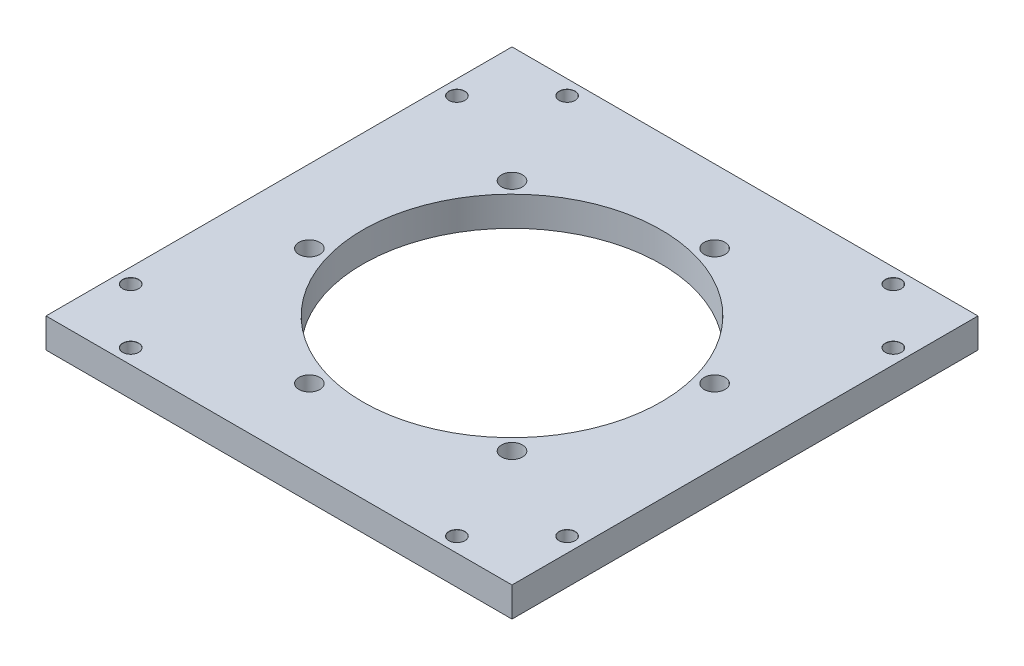
SolidWorks part; units mm, degrees
material "6061 Alloy"
ref_plane "Front Plane" through (0, 0, 0) normal (0, 0, 1) x (1, 0, 0)
ref_plane "Top Plane" through (0, 0, 0) normal (0, 1, 0) x (1, 0, 0)
ref_plane "Right Plane" through (0, 0, 0) normal (1, 0, 0) x (0, 0, -1)
sketch "Sketch1" plane through (0, 0, 0) normal (0, 1, 0) x (1, 0, 0)
  line L1 (-50, -50) -> (50, -50)
  line L2 (-50, -50) -> (-50, 50)
  line L3 (-50, 50) -> (50, 50)
  line L4 (50, -50) -> (50, 50)
  line L5 (-50, -50) -> (50, 50) construction
  line L6 (-50, 50) -> (50, -50) construction
  circle A1 centre (0, 0) radius 39.5
  arc A5 (-25.1023, 25.1023) -> (9.1881, 34.2904) centre (0, 0) cw
  arc A7 (9.1881, 34.2904) -> (-34.2904, -9.1881) centre (0, 0) ccw
  arc A9 (-34.2904, -9.1881) -> (-9.1881, -34.2904) centre (0, 0) ccw
  arc A11 (-9.1881, -34.2904) -> (25.1023, -25.1023) centre (0, 0) ccw
  circle A13 centre (0, 0) radius 32
  arc A14 (25.1023, -25.1023) -> (34.2904, 9.1881) centre (0, 0) ccw
extrude "Boss-Extrude3" add sketch "Sketch1" along normal blind 6.35 contours L1 L4 L3 L2 A1 | A1 A13 region at (-48.5858, 0, 0) region at (-38.3828, 0, 0)
hole_wizard "M4 Clearance Hole2" positions "Sketch6" profile "Sketch7" hole size "M4" standard "ANSI Metric" end condition through all
sketch "Sketch6" plane through (0, 0, 0) normal (0, -1, 0) x (-1, 0, 0)
  point P0 (-9.1881, 34.2904)
  point P3 (25.1023, 25.1023)
  point P6 (34.2904, -9.1881)
  point P9 (9.1881, -34.2904)
  point P12 (-25.1023, -25.1023)
  point P15 (-34.2904, 9.1881)
sketch "Sketch7" plane through (9.1881, 0, -34.2904) normal (1, 0, 0) x (0, 0, -1)
  line L0 (0, 0) -> (0, 6.35)
  line L1 (0, 6.35) -> (2.25, 6.35)
  line L2 (2.25, 6.35) -> (2.25, 0.025)
  line L3 (2.25, 0.025) -> (2.275, 0)
  line L5 (2.275, 0) -> (0, 0)
  line L6 (-2.25, 0.025) -> (-2.275, 0) construction
  line L11 (0, -6.35) -> (0, 107.95) construction
  dimension "Thru Hole Dia." = 4.5
  dimension "Thru Hole Depth" = 6.35
  dimension "Near C'Sink Dia." = 4.55
  dimension "Near C'Sink Angle" = 90
sketch "Sketch8" plane through (0, 6.35, 0) normal (0, 1, 0) x (1, 0, 0)
  line L0 (-50, -50) -> (-39.5, -50)
  line L1 (-50, -50) -> (50, -50) construction
  line L2 (-39.5, -50) -> (-39.5, -39.5)
  line L3 (50, -50) -> (39.5, -50)
  line L4 (39.5, -50) -> (39.5, -39.5)
  line L5 (50, 50) -> (39.5, 50)
  line L6 (-50, 50) -> (50, 50) construction
  line L7 (39.5, 50) -> (39.5, 39.5)
  line L8 (-50, 50) -> (-39.5, 50)
  line L9 (-50, -50) -> (-50, 50) construction
  line L10 (-39.5, 50) -> (-39.5, 39.5)
sketch "Sketch13" plane through (0, 6.35, 0) normal (0, 1, 0) x (1, 0, 0)
  line L1 (-50, -50) -> (-35, -50)
  line L2 (-50, -50) -> (50, -50) construction
  line L3 (-35, -50) -> (-35, -46.825)
  line L4 (-50, -50) -> (-50, -35)
  line L5 (-50, -50) -> (-50, 50) construction
  line L6 (-50, -35) -> (-46.825, -35)
  line L7 (-50, 50) -> (-35, 50)
  line L8 (-50, 50) -> (50, 50) construction
  line L9 (-35, 50) -> (-35, 46.825)
  line L10 (-50, 50) -> (-50, 35)
  line L11 (-50, 35) -> (-46.825, 35)
  line L13 (50, 50) -> (35, 50)
  line L14 (35, 50) -> (35, 46.825)
  line L15 (50, 50) -> (50, 35)
  line L16 (50, -50) -> (50, 50) construction
  line L17 (50, 35) -> (46.825, 35)
  line L18 (50, -50) -> (50, -35)
  line L19 (50, -35) -> (46.825, -35)
  line L20 (50, -50) -> (35, -50)
  line L21 (35, -50) -> (35, -46.825)
hole_wizard "M3 Clearance Hole1" positions "Sketch17" profile "Sketch18" hole size "M3" standard "ANSI Metric" end condition through all
sketch "Sketch17" plane through (0, 6.35, 0) normal (0, 1, 0) x (1, 0, 0)
  point P0 (-46.825, 35)
  point P3 (-35, 46.825)
  point P6 (35, 46.825)
  point P9 (46.825, 35)
  point P12 (46.825, -35)
  point P15 (35, -46.825)
  point P18 (-35, -46.825)
  point P21 (-46.825, -35)
sketch "Sketch18" plane through (-46.825, 6.35, -35) normal (1, 0, 0) x (0, 0, 1)
  line L0 (0, 0) -> (0, 6.35)
  line L1 (0, 6.35) -> (1.7, 6.35)
  line L2 (1.7, 6.35) -> (1.7, 0.025)
  line L3 (1.7, 0.025) -> (1.725, 0)
  line L5 (1.725, 0) -> (0, 0)
  line L6 (-1.7, 0.025) -> (-1.725, 0) construction
  line L11 (0, -6.35) -> (0, 107.95) construction
  dimension "Thru Hole Dia." = 3.4
  dimension "Thru Hole Depth" = 6.35
  dimension "Near C'Sink Dia." = 3.45
  dimension "Near C'Sink Angle" = 90
